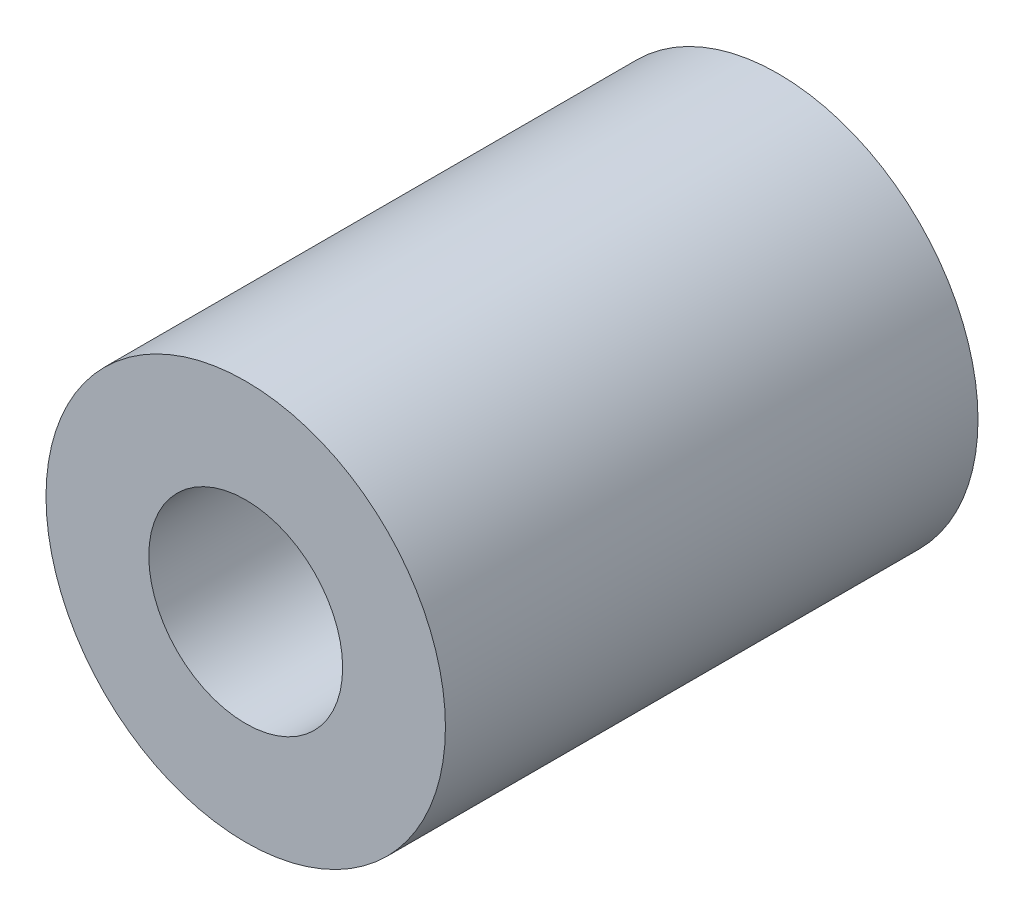
SolidWorks part; units mm, degrees
ref_plane "Front Plane" through (0, 0, 0) normal (0, 0, 1) x (1, 0, 0)
ref_plane "Top Plane" through (0, 0, 0) normal (0, 1, 0) x (1, 0, 0)
ref_plane "Right Plane" through (0, 0, 0) normal (1, 0, 0) x (0, 0, -1)
sketch "Sketch1" plane through (0, 0, 0) normal (0, 0, 1) x (1, 0, 0)
  circle A0 centre (0, 0) radius 2.3812
  circle A1 centre (0, 0) radius 1.1557
  dimension "OD" = 4.7625
  dimension "ID" = 2.3114
extrude "Extrude1" add sketch "Sketch1" along normal mid plane 6.35
sketch "Sketch2" plane through (0, 0, 0) normal (1, 0, 0) x (0, 0, -1)
  line L0 (-3.175, -1.1557) -> (3.175, -1.1557) construction
  line L3 (3.175, 1.1557) -> (-3.175, 1.1557) construction
  line L5 (-3.175, -1.1557) -> (3.175, -1.1557)
  line L6 (3.175, 1.1557) -> (-3.175, 1.1557)
sketch "Sketch4" plane through (0, 0, 3.175) normal (0, 0, 1) x (1, 0, 0)
  line L0 (0, 0) -> (-0.8172, 0.8172)
  line L1 (0, -0.8731) -> (0, 0.8731) construction
  circle A0 centre (0, 0) radius 1.1557 construction
  dimension "D1" = 45
